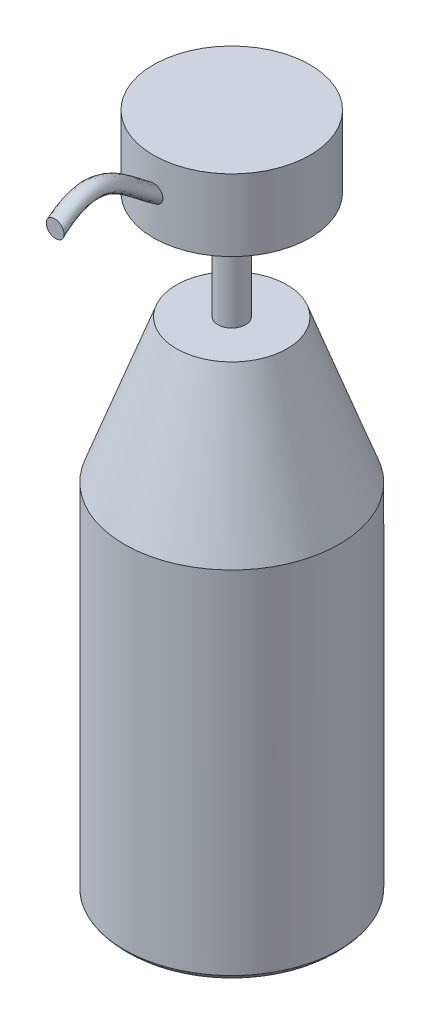
SolidWorks part; units mm, degrees
ref_plane "Front Plane" through (0, 0, 0) normal (0, 0, 1) x (1, 0, 0)
ref_plane "Top Plane" through (0, 0, 0) normal (0, 1, 0) x (1, 0, 0)
ref_plane "Right Plane" through (0, 0, 0) normal (1, 0, 0) x (0, 0, -1)
sketch "Sketch1" plane through (0, 0, 0) normal (0, 1, 0) x (1, 0, 0)
  circle A0 centre (0, 0) radius 30
  dimension "D1" = 60
extrude "Boss-Extrude1" add sketch "Sketch1" along normal blind 100
extrude "Boss-Extrude2" add sketch "Sketch1<2>" along normal blind 40 draft 20 from surface starting at face at (0, 100, 30)
sketch "Sketch1<2>" plane through (0, 0, 0) normal (0, 1, 0) x (1, 0, 0) same geometry as "Sketch1"
fillet "Fillet1" radius 2 1 edges at (0, 0, 30) second distance 2 conic rho 0.1 first distance on face at (0, 0, 30)
sketch "Sketch3" plane through (0, 140, 0) normal (0, 1, 0) x (1, 0, 0)
  circle A0 centre (0, 0) radius 3.8712
extrude "Boss-Extrude3" add sketch "Sketch3" along normal blind 30
sketch "Sketch4" plane through (0, 170, 0) normal (0, 1, 0) x (1, 0, 0)
  circle A0 centre (0, 0) radius 21.8656
extrude "Boss-Extrude4" add sketch "Sketch4" along normal blind 20
sketch "Sketch5" plane through (0, 0, 0) normal (0, 0, 1) x (1, 0, 0)
  circle A0 centre (0, 180.8448) radius 2.4869
  point P2 (0, 0)
sketch "Sketch7" plane through (0, 0, 0) normal (1, 0, 0) x (0, 0, -1)
  line L0 (0, 190) -> (0, 170.3662) construction
  line L1 (21.8656, 190) -> (-21.8656, 190) construction
  line L2 (-21.8656, 190) -> (-21.8656, 170) construction
  spline S0 degree 3 poles (0, 180.8448) (-21.7283, 164.0387) (-29.6034, 203.0119) (-49.2929, 185.9434) knots 0 0 0 0 1 1 1 1
  point P7 (0, 0)
  point P9 (-34.5031, 189.375)
  point P11 (-49.2929, 185.9434)
sweep "Sweep1" add profiles "Sketch5" path "Sketch7"
